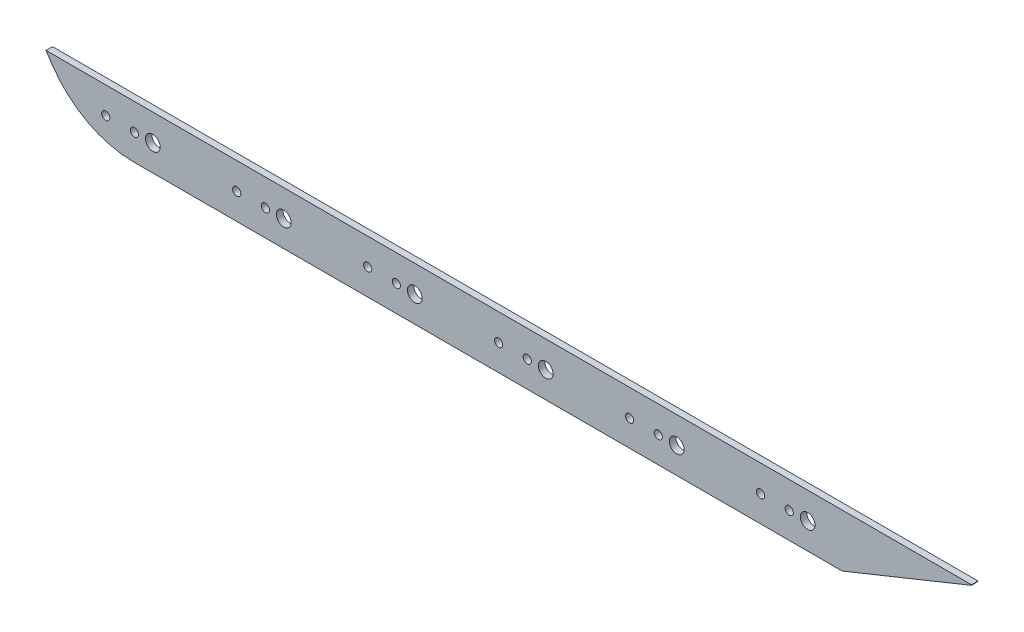
SolidWorks part; units mm, degrees
material "5052-H34"
ref_plane "Front Plane" through (0, 0, 0) normal (0, 0, 1) x (1, 0, 0)
ref_plane "Top Plane" through (0, 0, 0) normal (0, 1, 0) x (1, 0, 0)
ref_plane "Right Plane" through (0, 0, 0) normal (1, 0, 0) x (0, 0, -1)
sketch "Sketch1" plane through (0, 0, 0) normal (0, 0, 1) x (1, 0, 0)
  line L3 (428.1206, 28.9396) -> (0.5404, 28.9396)
  line L6 (-98.8794, 3.851) -> (-31.8794, -96.649)
  line L7 (428.1206, 28.9396) -> (403.1206, -71.149)
  line L9 (403.1206, -71.149) -> (366, -96.649)
  line L10 (-31.8794, -96.649) -> (366, -96.649)
  line L11 (0.5404, 28.9396) -> (-115.6052, 28.9396)
  line L12 (-98.8794, 3.851) -> (-115.6052, 28.9396)
  line L13 (-49.0861, -70.839) -> (403.198, -70.839)
  circle A0 centre (3.1206, -83.899) radius 3.6
  circle A1 centre (67.1206, -83.899) radius 3.6
  circle A2 centre (131.1206, -83.899) radius 3.6
  circle A3 centre (195.1206, -83.899) radius 3.6
  circle A4 centre (259.1206, -83.899) radius 3.6
  circle A5 centre (323.1206, -83.899) radius 3.6
  point P0 (-48.8794, -71.149)
  point P2 (-31.8794, -96.649)
  point P8 (48, -83.899)
  point P9 (403.1206, -71.149)
  point P23 (-49.0861, -70.839)
  point P25 (403.198, -70.839)
  dimension "D2" = 64
  dimension "D4" = 64
  dimension "D1" = 25.5
  dimension "D3" = 75
  dimension "D5" = 25
  dimension "D6" = 80
  dimension "D7" = 527
  dimension "D8" = 180
  dimension "D9" = 64
  dimension "D10" = 64
  dimension "D11" = 64
  dimension "D12" = 123.69
  dimension "D13" = 12.75
  dimension "D14" = 25.81
  dimension "D15" = 25.81
extrude "Boss-Extrude1" add sketch "Sketch1" along normal blind 3.175 contours L3 L11 L12 L6 L10 L9 L7
extrude "Cut-Extrude1" cut sketch "Sketch1<4>" along normal through all contours A0 | A1 | A2 | A3 | A4 | A5 region at (3.1206, -83.899, 0)
sketch "Sketch1<4>" plane through (0, 0, 0) normal (0, 0, 1) x (1, 0, 0) same geometry as "Sketch1"
sketch "Sketch5" plane through (0, 0, 0) normal (0, 0, -1) x (-1, 0, 0)
  line L0 (48.8794, -71.149) -> (-14.2353, -96.649)
  line L1 (31.8794, -96.649) -> (-366, -96.649) construction
  line L2 (-14.2353, -96.649) -> (31.8794, -96.649)
  line L3 (31.8794, -96.649) -> (48.8794, -71.149)
  line L6 (-366, -96.649) -> (-403.1206, -71.149)
  line L7 (-403.1206, -71.149) -> (-352, -71.149)
  line L9 (-352, -71.149) -> (-326.5, -96.649)
  line L11 (-366, -96.649) -> (-326.5, -96.649)
  dimension "D1" = 22
  dimension "D2" = 45
extrude "Cut-Extrude2" [suppressed] cut sketch "Sketch5" against normal up to next
fillet "Fillet1" radius 48 1 edges at (-31.8794, -96.649, 1.5875)
sketch "Sketch7" plane through (0, 0, 3.175) normal (0, 0, 1) x (1, 0, 0)
  line L0 (403.1206, -71.149) -> (340.0059, -96.649)
  line L1 (-31.8794, -96.649) -> (366, -96.649) construction
  line L2 (340.0059, -96.649) -> (366, -96.649)
  line L3 (366, -96.649) -> (403.1206, -71.149)
  dimension "D1" = 22
extrude "Cut-Extrude3" cut sketch "Sketch7" against normal blind 10
sketch "Sketch9" plane through (0, 0, 0) normal (0, 0, -1) x (-1, 0, 0)
  line L0 (-403.1206, -71.149) -> (48.8794, -71.149)
  line L1 (48.8794, -71.149) -> (48.8794, -114.9143)
  line L2 (48.8794, -114.9143) -> (-403.1206, -114.9143)
  line L3 (-403.1206, -114.9143) -> (-403.1206, -71.149)
extrude "Cut-Extrude4" [suppressed] cut sketch "Sketch9" against normal blind 10
sketch "Sketch11" plane through (0, 0, 3.175) normal (0, 0, 1) x (1, 0, 0)
  line L0 (-49.0861, -70.839) -> (403.198, -70.839) construction
  line L1 (-49.0861, -70.839) -> (403.198, -70.839)
  line L3 (-115.6052, 28.9396) -> (428.1206, 28.9396)
  line L4 (428.1206, 28.9396) -> (403.198, -70.839)
  line L5 (-49.0861, -70.839) -> (-115.6052, 28.9396)
extrude "Cut-Extrude5" cut sketch "Sketch11" against normal blind 10
sketch "Sketch13" plane through (0, 0, 0) normal (0, 0, -1) x (-1, 0, 0)
  circle A0 centre (-58.1206, -83.8863) radius 2
  circle A1 centre (-44.1206, -83.8863) radius 2
  circle A2 centre (5.8794, -83.8863) radius 2
  circle A3 centre (19.8794, -83.8863) radius 2
  circle A6 centre (-122.1206, -83.899) radius 2
  circle A7 centre (-108.1206, -83.899) radius 2
  circle A8 centre (-186.1206, -83.899) radius 2
  circle A9 centre (-172.1206, -83.899) radius 2
  circle A10 centre (-250.1206, -83.899) radius 2
  circle A11 centre (-236.1206, -83.899) radius 2
  circle A12 centre (-314.1206, -83.899) radius 2
  circle A13 centre (-300.1206, -83.899) radius 2
  point P16 (0, 0)
  point P31 (-319.5568, -32.2297)
  dimension "D1" = 9
  dimension "D2" = 4
  dimension "D7" = 4
  dimension "D8" = 4
  dimension "D9" = 14
  dimension "D3" = 9
  dimension "D4" = 9
  dimension "D5" = 14
  dimension "D6" = 14
  dimension "D10" = 9
  dimension "D11" = 14
  dimension "D12" = 9
  dimension "D13" = 14
  dimension "D14" = 9
  dimension "D15" = 14
extrude "Cut-Extrude6" cut sketch "Sketch13" against normal blind 10
